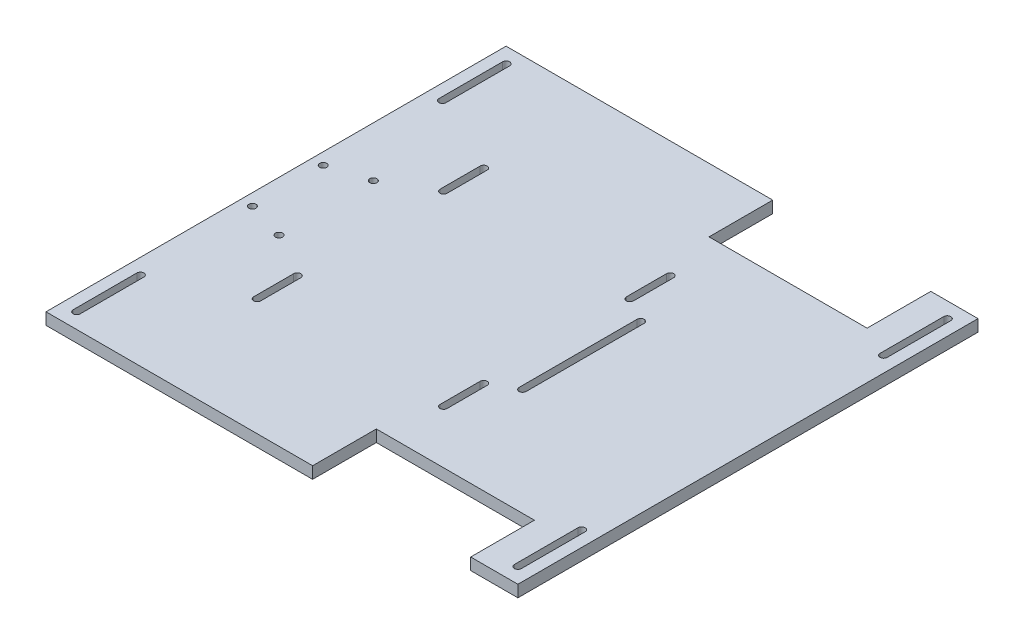
SolidWorks part; units mm, degrees
ref_plane "Front Plane" through (0, 0, 0) normal (0, 0, 1) x (1, 0, 0)
ref_plane "Top Plane" through (0, 0, 0) normal (0, 1, 0) x (1, 0, 0)
ref_plane "Right Plane" through (0, 0, 0) normal (1, 0, 0) x (0, 0, -1)
sketch "Sketch2" plane through (0, 0, 0) normal (0, 1, 0) x (1, 0, 0)
  line L1 (-100, -97.5) -> (100, -97.5)
  line L2 (-100, -97.5) -> (-100, 97.5)
  line L3 (-100, 97.5) -> (100, 97.5)
  line L4 (100, -97.5) -> (100, 97.5)
  line L5 (-100, -97.5) -> (100, 97.5) construction
  line L6 (-100, 97.5) -> (100, -97.5) construction
  point P0 (0, 0)
  dimension "D1" = 200
  dimension "D2" = 195
extrude "Boss-Extrude1" add sketch "Sketch2" along normal blind 5
sketch "Sketch3" plane through (0, 5, 0) normal (0, 1, 0) x (1, 0, 0)
  line L0 (-100, 0) -> (100, 0) construction
  line L1 (-100, 97.5) -> (-100, -97.5) construction
  line L2 (100, -97.5) -> (100, 97.5) construction
  line L3 (0, -97.5) -> (0, 97.5) construction
  line L4 (-100, -97.5) -> (100, -97.5) construction
  line L5 (100, 97.5) -> (-100, 97.5) construction
  line L6 (-93.5, -91) -> (-93.5, -64) construction
  line L7 (-95, -91) -> (-95, -64)
  line L8 (-92, -91) -> (-92, -64)
  line L9 (-93.5, 91) -> (-93.5, 64) construction
  line L10 (-95, 91) -> (-95, 64)
  line L11 (-92, 91) -> (-92, 64)
  line L12 (93.5, 91) -> (93.5, 64) construction
  line L13 (95, 91) -> (95, 64)
  line L14 (92, 91) -> (92, 64)
  line L15 (93.5, -91) -> (93.5, -64) construction
  line L16 (95, -91) -> (95, -64)
  line L17 (92, -91) -> (92, -64)
  arc A0 (-95, -91) -> (-92, -91) centre (-93.5, -91) ccw
  arc A1 (-92, -64) -> (-95, -64) centre (-93.5, -64) ccw
  arc A2 (-95, 91) -> (-92, 91) centre (-93.5, 91) cw
  arc A3 (-92, 64) -> (-95, 64) centre (-93.5, 64) cw
  arc A4 (95, 91) -> (92, 91) centre (93.5, 91) ccw
  arc A5 (92, 64) -> (95, 64) centre (93.5, 64) ccw
  arc A6 (95, -91) -> (92, -91) centre (93.5, -91) cw
  arc A7 (92, -64) -> (95, -64) centre (93.5, -64) cw
  point P14 (-93.5, -77.5)
  point P21 (-93.5, 77.5)
  point P28 (93.5, 77.5)
  point P35 (93.5, -77.5)
  dimension "D2" = 1.5
  dimension "D3" = 5
  dimension "D4" = 6.5
  dimension "D1" = 27
extrude "Cut-Extrude1" cut sketch "Sketch3" against normal through all
sketch "Sketch4" plane through (0, 0, 0) normal (0, -1, 0) x (1, 0, 0)
  line L0 (-100, 0) -> (100, 0) construction
  line L1 (-100, -97.5) -> (-100, 97.5) construction
  line L2 (100, 97.5) -> (100, -97.5) construction
  line L3 (100, -97.5) -> (-100, -97.5) construction
  line L4 (13, -97.5) -> (80, -97.5)
  line L5 (13, -97.5) -> (13, -70.5)
  line L6 (13, -70.5) -> (80, -70.5)
  line L7 (80, -97.5) -> (80, -70.5)
  line L8 (80, 97.5) -> (80, 70.5)
  line L9 (13, 97.5) -> (80, 97.5)
  line L10 (13, 70.5) -> (80, 70.5)
  line L11 (13, 97.5) -> (13, 70.5)
  dimension "D1" = 27
  dimension "D2" = 67
  dimension "D3" = 20
extrude "Cut-Extrude2" cut sketch "Sketch4" against normal through all
sketch "Sketch5" plane through (0, 0, 0) normal (0, -1, 0) x (1, 0, 0)
  line L0 (-100, 0) -> (100, 0) construction
  line L1 (-100, -97.5) -> (-100, 97.5) construction
  line L2 (100, 97.5) -> (100, -97.5) construction
  line L3 (13, -70.5) -> (13, -97.5) construction
  line L4 (23, -52) -> (-64, -52)
  line L5 (23, -52) -> (23, 52)
  line L6 (23, 52) -> (-64, 52)
  line L7 (-64, -52) -> (-64, 52)
  line L8 (23, -52) -> (-64, 52) construction
  line L9 (23, 52) -> (-64, -52) construction
  line L10 (-60, -48) -> (-60, -31) construction
  line L11 (-61.5, -48) -> (-61.5, -31)
  line L12 (-58.5, -48) -> (-58.5, -31)
  line L13 (-60, 48) -> (-60, 31) construction
  line L14 (-61.5, 48) -> (-61.5, 31)
  line L15 (-58.5, 48) -> (-58.5, 31)
  line L16 (-20.5, -52) -> (-20.5, 52) construction
  line L17 (19, 48) -> (19, 31) construction
  line L18 (20.5, 48) -> (20.5, 31)
  line L19 (17.5, 48) -> (17.5, 31)
  line L20 (19, -48) -> (19, -31) construction
  line L21 (20.5, -48) -> (20.5, -31)
  line L22 (17.5, -48) -> (17.5, -31)
  arc A0 (-61.5, -48) -> (-58.5, -48) centre (-60, -48) ccw
  arc A1 (-58.5, -31) -> (-61.5, -31) centre (-60, -31) ccw
  arc A2 (-61.5, 48) -> (-58.5, 48) centre (-60, 48) cw
  arc A3 (-58.5, 31) -> (-61.5, 31) centre (-60, 31) cw
  arc A4 (20.5, 48) -> (17.5, 48) centre (19, 48) ccw
  arc A5 (17.5, 31) -> (20.5, 31) centre (19, 31) ccw
  arc A6 (20.5, -48) -> (17.5, -48) centre (19, -48) cw
  arc A7 (17.5, -31) -> (20.5, -31) centre (19, -31) cw
  point P6 (-20.5, 0)
  point P15 (-60, -39.5)
  point P22 (-60, 39.5)
  point P31 (19, 39.5)
  point P38 (19, -39.5)
  dimension "D5" = 1.5
  dimension "D1" = 104
  dimension "D2" = 87
  dimension "D3" = 10
  dimension "D4" = 17
  dimension "D6" = 2.5
  dimension "D7" = 4
extrude "Cut-Extrude4" cut sketch "Sketch5" against normal through all contours L11 A1 L12 A0 | L14 A3 L15 A2 | L19 A5 L18 A4 | L22 A7 L21 A6
sketch "Sketch7" plane through (0, 0, 0) normal (0, -1, 0) x (1, 0, 0)
  line L0 (29.5, -25) -> (29.5, 25) construction
  line L1 (-100, 0) -> (100, 0) construction
  line L2 (28, -25) -> (28, 25)
  line L3 (31, -25) -> (31, 25)
  line L4 (23, -52) -> (23, 52) construction
  arc A0 (28, -25) -> (31, -25) centre (29.5, -25) ccw
  arc A1 (31, 25) -> (28, 25) centre (29.5, 25) ccw
  point P4 (29.5, 0)
  dimension "D2" = 1.5
  dimension "D1" = 50
  dimension "D3" = 5
extrude "Cut-Extrude5" cut sketch "Sketch7" against normal through all
sketch "Sketch8" plane through (0, 5, 0) normal (0, 1, 0) x (1, 0, 0)
  line L0 (-100, 0) -> (100, 0) construction
  line L1 (-100, 97.5) -> (-100, -97.5) construction
  line L2 (100, -97.5) -> (100, 97.5) construction
  line L3 (-78.75, -25) -> (-78.75, 25) construction
  line L4 (-95, -25) -> (-62.5, -25)
  line L5 (-95, -25) -> (-95, 25)
  line L6 (-95, 25) -> (-62.5, 25)
  line L7 (-62.5, -25) -> (-62.5, 25)
  line L8 (-95, -25) -> (-62.5, 25) construction
  line L9 (-95, 25) -> (-62.5, -25) construction
  circle A0 centre (-78.75, -19.995) radius 1.5
  circle A1 centre (-78.75, 19.995) radius 1.5
  point P6 (-78.75, 0)
  dimension "D4" = 3
  dimension "D1" = 32.5
  dimension "D2" = 50
  dimension "D3" = 5
  dimension "D5" = 39.99
extrude "Cut-Extrude6" cut sketch "Sketch8" against normal through all contours A1 | A0 region at (-78.75, 5, -19.995)
sketch "Sketch9" plane through (0, 5, 0) normal (0, 1, 0) x (1, 0, 0)
  line L0 (-100, 0) -> (100, 0) construction
  line L1 (-100, 97.5) -> (-100, -97.5) construction
  line L2 (100, -97.5) -> (100, 97.5) construction
  line L4 (-100, -25) -> (-90, -25)
  line L5 (-100, -25) -> (-100, 25)
  line L6 (-100, 25) -> (-90, 25)
  line L7 (-90, -25) -> (-90, 25)
  line L8 (-100, -25) -> (-90, 25) construction
  line L9 (-100, 25) -> (-90, -25) construction
  circle A0 centre (-95, 15) radius 1.5
  circle A1 centre (-95, -15) radius 1.5
  point P6 (-95, 0)
  dimension "D4" = 3
  dimension "D1" = 10
  dimension "D2" = 0
  dimension "D3" = 50
  dimension "D5" = 30
  dimension "D6" = 5
extrude "Cut-Extrude7" cut sketch "Sketch9" against normal through all contours A0 | A1
